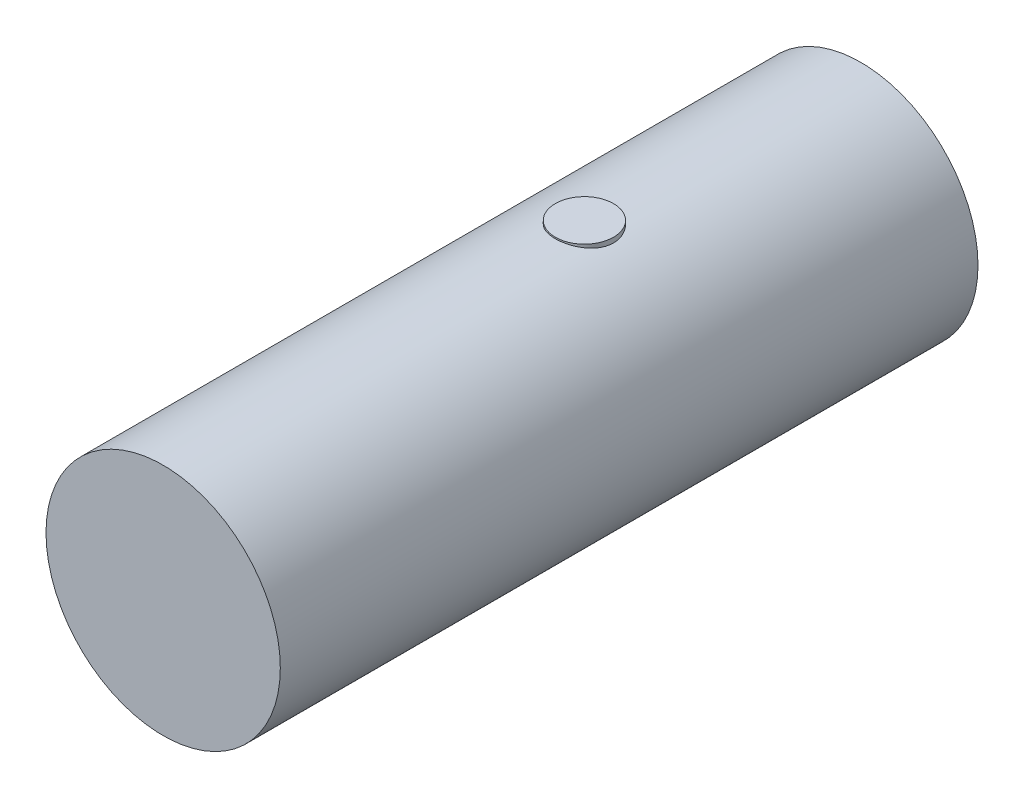
SolidWorks part; units mm, degrees
ref_plane "Ebene vorne" through (0, 0, 0) normal (0, 0, 1) x (1, 0, 0)
ref_plane "Ebene oben" through (0, 0, 0) normal (0, 1, 0) x (1, 0, 0)
ref_plane "Ebene rechts" through (0, 0, 0) normal (1, 0, 0) x (0, 0, -1)
sketch "Skizze1" plane through (0, 0, 0) normal (0, 0, 1) x (1, 0, 0)
  circle A0 centre (0, 0) radius 89
  dimension "D1" = 178
extrude "Aufsatz-Linear austragen1" add sketch "Skizze1" along normal blind 530
sketch "Skizze2" plane through (0, 0, 0) normal (0, 1, 0) x (1, 0, 0)
  line L0 (0, 0) -> (0, -530) construction
  line L1 (-89, -530) -> (89, -530) construction
  line L2 (89, 0) -> (-89, 0) construction
  circle A0 centre (0, -210) radius 22.1266
  dimension "D1" = 210
extrude "Aufsatz-Linear austragen2" add sketch "Skizze2" along normal blind 90 and the other way blind 90
